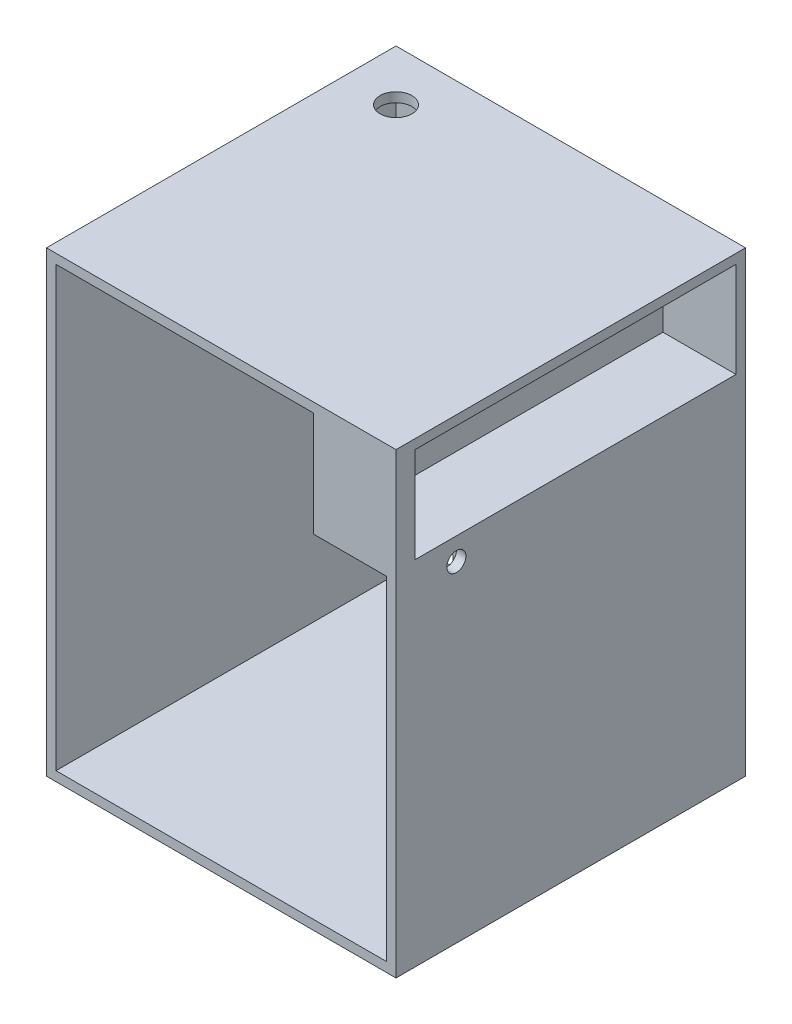
SolidWorks part; units mm, degrees
material "Balsa"
ref_plane "Alzado" through (0, 0, 0) normal (0, 0, 1) x (1, 0, 0)
ref_plane "Planta" through (0, 0, 0) normal (0, 1, 0) x (1, 0, 0)
ref_plane "Vista lateral" through (0, 0, 0) normal (1, 0, 0) x (0, 0, -1)
sketch "Croquis1" plane through (0, 0, 0) normal (0, 1, 0) x (1, 0, 0)
  line L1 (275, -275) -> (-275, -275)
  line L2 (275, -275) -> (275, 275)
  line L3 (275, 275) -> (-275, 275)
  line L4 (-275, -275) -> (-275, 275)
  line L5 (275, -275) -> (-275, 275) construction
  line L6 (275, 275) -> (-275, -275) construction
  point P0 (0, 0)
  dimension "D1" = 550
  dimension "D2" = 550
extrude "Saliente-Extruir1" add sketch "Croquis1" along normal blind 720
shell "Vaciado1" thickness 15 removed face at (0, 360, 275)
sketch "Croquis2" plane through (0, 0, 275) normal (0, 0, 1) x (1, 0, 0)
  line L11 (160, 705) -> (160, 555)
  line L17 (-260, 705) -> (260, 705) construction
  line L18 (160, 555) -> (260, 555)
  line L19 (260, 705) -> (260, 15) construction
  line L20 (145, 705) -> (145, 540)
  line L21 (145, 540) -> (260, 540)
  line L22 (145, 705) -> (160, 705)
  line L23 (260, 555) -> (260, 540)
  dimension "D1" = 100
  dimension "D2" = 150
  dimension "D3" = 15
extrude "Saliente-Extruir2" add sketch "Croquis2" against normal up to vertex (535 mm away) up to point (260, 705, -260)
sketch "Croquis3" plane through (275, 0, 0) normal (1, 0, 0) x (0, 0, -1)
  line L0 (-275, 705) -> (260, 705) construction
  line L1 (-245, 705) -> (260, 705)
  line L2 (-245, 705) -> (-245, 555)
  line L3 (-245, 555) -> (260, 555)
  line L4 (260, 705) -> (260, 555)
  line L5 (260, 555) -> (-275, 555) construction
  line L6 (260, 705) -> (260, 555) construction
  line L8 (-275, 720) -> (-275, 0) construction
  dimension "D1" = 30
extrude "Cortar-Extruir1" cut sketch "Croquis3" against normal up to surface (115 mm away) up to face at (160, 630, 7.5)
sketch "Croquis4" plane through (160, 0, 0) normal (1, 0, 0) x (0, 0, -1)
  line L1 (-275, 705) -> (-260, 705)
  line L2 (-275, 705) -> (-275, 555)
  line L3 (-275, 555) -> (-260, 555)
  line L4 (-260, 705) -> (-260, 555)
  dimension "D1" = 15
extrude "Saliente-Extruir3" add sketch "Croquis4" along normal up to vertex (100 mm away) up to point (260, 555, 275)
sketch "Croquis5" plane through (-275, 0, 0) normal (-1, 0, 0) x (0, 0, 1)
  line L1 (-275, 720) -> (-275, 0) construction
  line L2 (-275, 720) -> (275, 720) construction
  circle A0 centre (-180, 520) radius 15
  dimension "D2" = 30
  dimension "D1" = 95
  dimension "D3" = 200
extrude "Cortar-Extruir2" cut sketch "Croquis5" against normal blind 30
sketch "Croquis6" plane through (275, 0, 0) normal (1, 0, 0) x (0, 0, -1)
  line L0 (-275, 720) -> (-275, 0) construction
  line L1 (-275, 720) -> (275, 720) construction
  circle A0 centre (-180, 520) radius 15
  dimension "D3" = 30
  dimension "D1" = 95
  dimension "D2" = 200
extrude "Cortar-Extruir3" cut sketch "Croquis6" against normal blind 30
sketch "Croquis7" plane through (0, 0, -275) normal (0, 0, -1) x (-1, 0, 0)
  line L0 (-275, 0) -> (275, 0) construction
  line L1 (275, 720) -> (275, 0) construction
  circle A0 centre (195, 80) radius 25
  point P6 (352.268, 130.9881)
  dimension "D3" = 50
  dimension "D1" = 80
  dimension "D2" = 80
extrude "Cortar-Extruir4" cut sketch "Croquis7" against normal blind 25
sketch "Croquis8" plane through (0, 720, 0) normal (0, 1, 0) x (1, 0, 0)
  line L0 (-275, 275) -> (-275, -275) construction
  line L1 (275, 275) -> (-275, 275) construction
  circle A0 centre (-195, 195) radius 25
  dimension "D1" = 50
  dimension "D2" = 80
  dimension "D3" = 80
extrude "Cortar-Extruir5" cut sketch "Croquis8" against normal blind 25
sketch "Croquis10" plane through (160, 0, 0) normal (1, 0, 0) x (0, 0, -1)
  line L0 (260, 555) -> (260, 705) construction
  line L1 (260, 705) -> (-260, 705) construction
  circle A0 centre (210, 655) radius 25
  dimension "D3" = 50
  dimension "D1" = 50
  dimension "D2" = 50
extrude "Cortar-Extruir6" cut sketch "Croquis10" against normal blind 25
